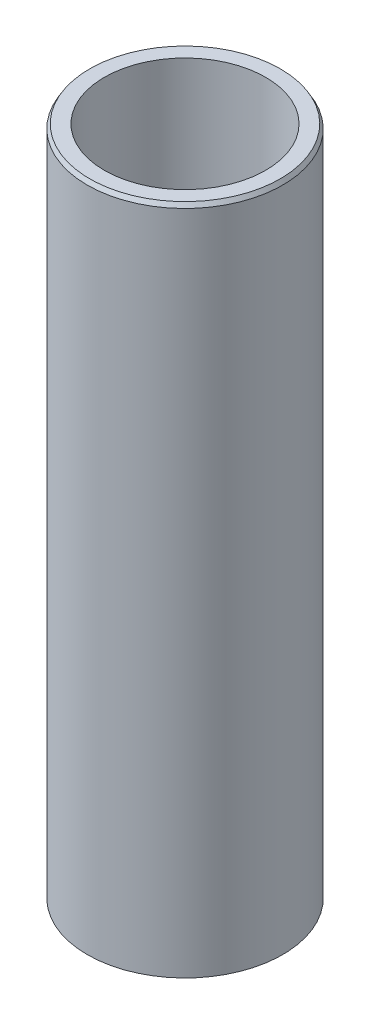
SolidWorks part; units mm, degrees
ref_plane "Front Plane" through (0, 0, 0) normal (0, 0, 1) x (1, 0, 0)
ref_plane "Top Plane" through (0, 0, 0) normal (0, 1, 0) x (1, 0, 0)
ref_plane "Right Plane" through (0, 0, 0) normal (1, 0, 0) x (0, 0, -1)
sketch "Sketch1" plane through (0, 0, 0) normal (0, 1, 0) x (1, 0, 0)
  circle A0 centre (0, 0) radius 42.5
  dimension "SHAFT_OD" = 85
extrude "Boss-Extrude1" add sketch "Sketch1" along normal blind 292.6765
sketch "Sketch2" plane through (0, 0, 0) normal (0, 1, 0) x (1, 0, 0)
  circle A0 centre (0, 0) radius 35.0735
  dimension "BORE_D" = 70.1471
extrude "Cut-Extrude1" cut sketch "Sketch2" along normal through all
chamfer "Chamfer1" distance 1.8359 angle 30 2 edges at (0, 292.6765, 42.5) (0, 0, 42.5) first distance on face at (0, 292.6765, 42.5) first distance on face at (0, 0, 35.0735)
